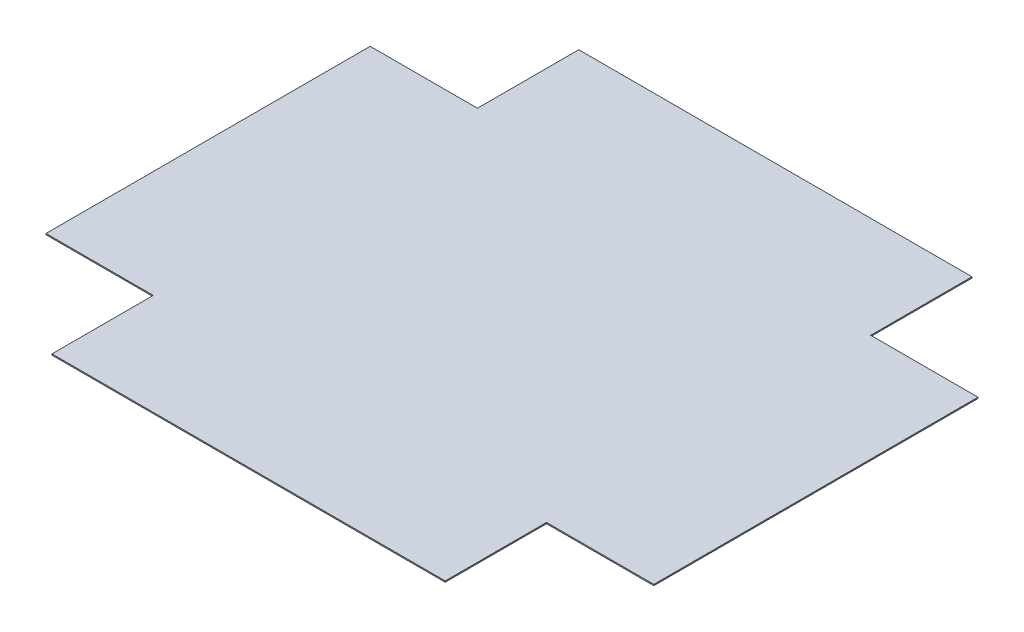
SolidWorks part; units mm, degrees
ref_plane "Front" through (0, 0, 0) normal (0, 0, 1) x (1, 0, 0)
ref_plane "Top" through (0, 0, 0) normal (0, 1, 0) x (1, 0, 0)
ref_plane "Right" through (0, 0, 0) normal (1, 0, 0) x (0, 0, -1)
sketch "Sketch1" plane through (0, 0, 0) normal (0, 1, 0) x (1, 0, 0)
  line L0 (-127, 101.6) -> (127, 101.6) construction
  line L1 (-127, -101.6) -> (127, -101.6) construction
  line L2 (-127, -101.6) -> (-127, 101.6) construction
  line L3 (-127, 101.6) -> (-123.25, 101.6)
  line L4 (127, -101.6) -> (127, 101.6) construction
  line L5 (-127, -101.6) -> (127, 101.6) construction
  line L6 (-127, 101.6) -> (127, -101.6) construction
  line L7 (-190.5, 165.1) -> (190.5, 165.1) construction
  line L8 (-190.5, 165.1) -> (-190.5, -165.1) construction
  line L9 (-190.5, -165.1) -> (190.5, -165.1) construction
  line L10 (190.5, 165.1) -> (190.5, -165.1) construction
  line L11 (-190.5, 165.1) -> (190.5, -165.1) construction
  line L12 (-190.5, -165.1) -> (190.5, 165.1) construction
  line L13 (-123.25, 165.1) -> (123.25, 165.1)
  line L14 (-123.25, 101.6) -> (-123.25, 165.1)
  line L15 (127, 101.6) -> (190.5, 101.6)
  line L16 (190.5, 101.6) -> (190.5, -101.6)
  line L17 (190.5, -101.6) -> (127, -101.6)
  line L18 (127, -101.6) -> (123.25, -101.6)
  line L19 (123.25, -165.1) -> (-123.25, -165.1)
  line L20 (123.25, -101.6) -> (123.25, -165.1)
  line L21 (-127, -101.6) -> (-190.5, -101.6)
  line L22 (-190.5, -101.6) -> (-190.5, 101.6)
  line L23 (-190.5, 101.6) -> (-127, 101.6)
  line L24 (-127, -101.6) -> (-123.25, -101.6)
  line L25 (-123.25, -101.6) -> (-123.25, -165.1)
  line L26 (127, 101.6) -> (123.25, 101.6)
  line L27 (123.25, 101.6) -> (123.25, 165.1)
  point P0 (0, 0)
  point P3 (0, 0)
sheet metal parameters "Sheet-Metal1" thickness 0.7366 parameters "D1"=0.7937
base flange "Base-Flange1" sketch "Sketch1" thickness 0.7366 reverse thickness direction no parameters "D1"=0.7937
sketch "Sketch6" plane through (0, 0, 0) normal (0, 1, 0) x (1, 0, 0)
  line L0 (-123.25, 101.6) -> (123.25, 101.6)
  line L2 (-123.25, -101.6) -> (123.25, -101.6)
sketch "Sketch4" plane through (0, 0, 0) normal (0, 1, 0) x (1, 0, 0)
  line L0 (-127, -101.6) -> (-127, 101.6)
  line L2 (127, 101.6) -> (127, -101.6)
flat pattern "Flat-Pattern1" [suppressed]
sketch "Bend-Lines1" plane through (0, 0, 0) normal (0, 1, 0) x (1, 0, 0)
sketch3d "Bounding-Box1" [suppressed]
  line L0 (-190.5, 165.1, 0) -> (190.5, 165.1, 0) construction
  line L1 (-190.5, -165.1, 0) -> (190.5, -165.1, 0) construction
  line L2 (-190.5, 165.1, 0) -> (-190.5, -165.1, 0) construction
  line L3 (190.5, 165.1, 0) -> (190.5, -165.1, 0) construction
